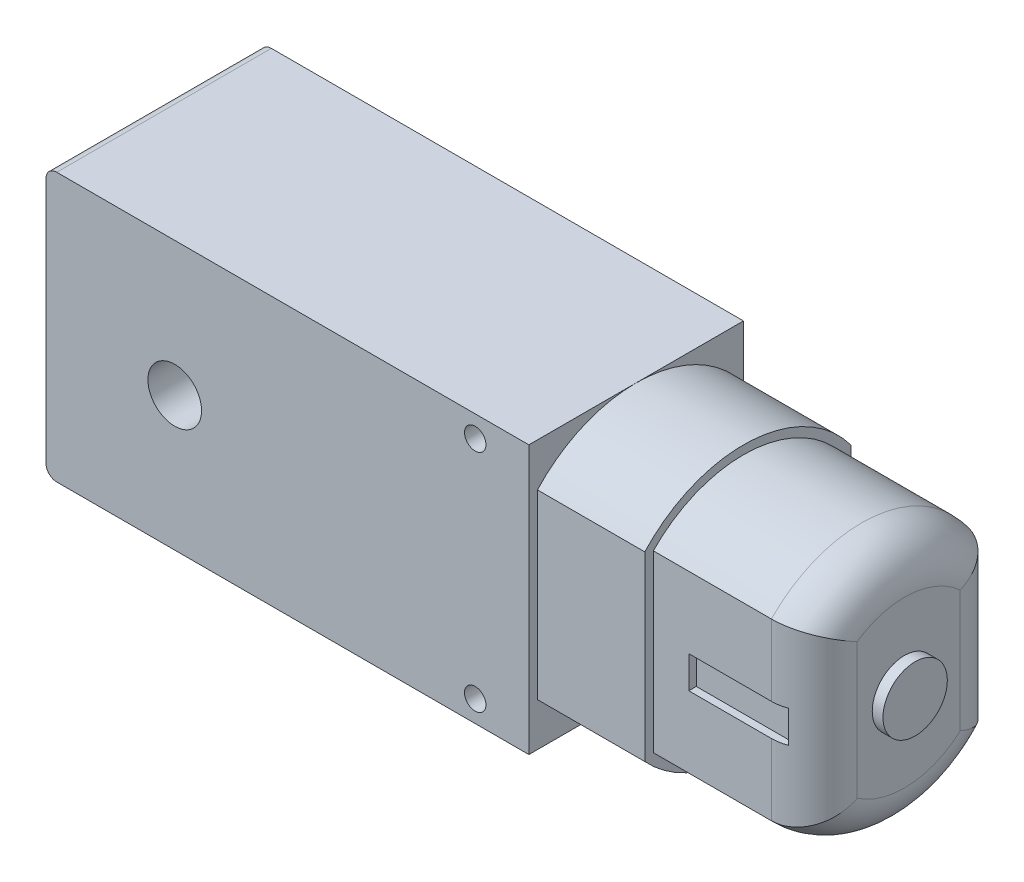
SolidWorks part; units mm, degrees
ref_plane "Front Plane" through (0, 0, 0) normal (0, 0, 1) x (1, 0, 0)
ref_plane "Top Plane" through (0, 0, 0) normal (0, 1, 0) x (1, 0, 0)
ref_plane "Right Plane" through (0, 0, 0) normal (1, 0, 0) x (0, 0, -1)
sketch "Sketch1" plane through (0, 0, 0) normal (0, 0, 1) x (1, 0, 0)
  line L1 (35, -12.5) -> (-35, -12.5)
  line L2 (35, -12.5) -> (35, 12.5)
  line L3 (35, 12.5) -> (-35, 12.5)
  line L4 (-35, -12.5) -> (-35, 12.5)
  line L5 (35, -12.5) -> (-35, 12.5) construction
  line L6 (35, 12.5) -> (-35, -12.5) construction
  point P0 (0, 0)
  dimension "D1" = 70
  dimension "D2" = 25
extrude "Boss-Extrude1" add sketch "Sketch1" along normal mid plane 20
sketch "Sketch2" plane through (35, 0, 0) normal (1, 0, 0) x (0, 0, -1)
  line L1 (-10, -7.5) -> (-10, -12.5)
  line L2 (10, 7.5) -> (10, 12.5)
  line L5 (10, -12.5) -> (10, 12.5)
  line L6 (10, 12.5) -> (-10, 12.5)
  line L7 (-10, 12.5) -> (-10, -12.5)
  line L8 (-10, -12.5) -> (10, -12.5)
  line L9 (10, -12.5) -> (10, -7.5)
  line L10 (10, 12.5) -> (-10, 12.5)
  line L11 (-10, 12.5) -> (-10, 7.5)
  line L12 (-10, -12.5) -> (10, -12.5)
  arc A0 (-10, -7.5) -> (10, -7.5) centre (0, 0) ccw
  arc A1 (10, 7.5) -> (-10, 7.5) centre (0, 0) ccw
  line M6 (10, -12.5) -> (10, 12.5)
  line M7 (10, 12.5) -> (-10, 12.5)
  line M8 (-10, 12.5) -> (-10, -12.5)
  line M9 (-10, -12.5) -> (10, -12.5)
  dimension "D1" = 0
extrude "Cut-Extrude2" cut sketch "Sketch2" against normal blind 25 contours A1 L10 M8 | A1 M6 M7 | A0 L12 M6 | A0 M8 M9 region at (35, -11.0705, 7.611) region at (35, 11.0705, 7.611) region at (35, -11.0705, -7.611) region at (35, 11.0705, -7.611)
sketch "Sketch4" plane through (35, 0, 0) normal (1, 0, 0) x (0, 0, -1)
  line L0 (-9.2, 8.4623) -> (-9.2, -8.4623)
  line L1 (-10, -7.5) -> (-10, 7.5) construction
  line L2 (-9.2, 8.4623) -> (-11.6207, 8.4623)
  line L3 (-11.6207, 8.4623) -> (-11.6207, -8.4623)
  line L4 (-11.6207, -8.4623) -> (-9.2, -8.4623)
  arc A0 (10, 7.5) -> (-10, 7.5) centre (0, 0) ccw construction
  arc A1 (-10, -7.5) -> (10, -7.5) centre (0, 0) ccw construction
  dimension "D1" = 0.8
extrude "Cut-Extrude3" cut sketch "Sketch4" against normal blind 25
sketch "Sketch5" plane through (35, 0, 0) normal (1, 0, 0) x (0, 0, -1)
  line L2 (-8.4, 8.1443) -> (-8.4, -8.1443)
  line L3 (9.2, -7.2284) -> (9.2, 7.2284)
  line L4 (-9.2, 8.4623) -> (-9.2, -8.4623)
  line L5 (10, -7.5) -> (10, 7.5)
  line L6 (-9.2, 8.4623) -> (-9.2, -8.4623)
  line L7 (10, -7.5) -> (10, 7.5)
  arc A2 (9.2, 7.2284) -> (-8.4, 8.1443) centre (0, 0) ccw
  arc A3 (-8.4, -8.1443) -> (9.2, -7.2284) centre (0, 0) ccw
  arc A4 (10, 7.5) -> (-9.2, 8.4623) centre (0, 0) ccw
  arc A5 (-9.2, -8.4623) -> (10, -7.5) centre (0, 0) ccw
  arc A6 (10, 7.5) -> (-9.2, 8.4623) centre (0, 0) ccw
  arc A7 (-9.2, -8.4623) -> (10, -7.5) centre (0, 0) ccw
  dimension "D1" = 0
  dimension "D2" = 0.8
extrude "Cut-Extrude4" cut sketch "Sketch5" against normal blind 15
fillet "Fillet1" radius 4 4 edges at (35, 0, -9.2) (35, -11.6842, -0.608) (35, 0, 8.4) (35, 11.6842, -0.608)
sketch "Sketch6" plane through (35, 0, 0) normal (1, 0, 0) x (0, 0, -1)
  circle A0 centre (0, 0) radius 3
  dimension "D1" = 6
extrude "Boss-Extrude2" add sketch "Sketch6" along normal blind 1
sketch "Sketch7" plane through (0, 0, -9.2) normal (0, 0, -1) x (-1, 0, 0)
  line L0 (-31, 7.2284) -> (-31, -7.2284) construction
  line L1 (-32.3651, -1.5) -> (-23.3004, -1.5)
  line L2 (-32.3651, -1.5) -> (-32.3651, 1.5)
  line L3 (-32.3651, 1.5) -> (-23.3004, 1.5)
  line L4 (-23.3004, -1.5) -> (-23.3004, 1.5)
  point P6 (-31, 0)
  point P7 (-23.3004, 0)
  dimension "D1" = 3
extrude "Cut-Extrude5" cut sketch "Sketch7" against normal blind 1.5
mirror "Mirror1" about plane through (0, 0, 0) normal (0, 0, 1) of "Cut-Extrude5"
fillet "Fillet2" radius 1 2 edges at (-35, 12.5, 0) (-35, -12.5, 0)
sketch "Sketch8" plane through (0, 0, 0) normal (0, 0, 1) x (1, 0, 0)
  line L0 (-35, 11.5) -> (-35, -11.5) construction
  line L1 (-35, -2.5) -> (-40, -2.5)
  line L2 (-35, -2.5) -> (-35, 2.5)
  line L3 (-35, 2.5) -> (-40, 2.5)
  line L4 (-40, -2.5) -> (-40, 2.5)
  circle A0 centre (-37.5, 0) radius 1.5
  point P6 (-40, 0)
  dimension "D3" = 3
  dimension "D1" = 5
  dimension "D2" = 5
extrude "Boss-Extrude3" add sketch "Sketch8" along normal mid plane 3.5
sketch "Sketch9" plane through (0, 0, 10) normal (0, 0, 1) x (1, 0, 0)
  line L0 (8.2693, 0) -> (-21.3687, 0) construction
  line L1 (-34, -12.5) -> (10, -12.5) construction
  line L2 (-35, 11.5) -> (-35, -11.5) construction
  circle A0 centre (5, -10.5) radius 1
  circle A1 centre (5, 10.5) radius 1
  dimension "D1" = 2
  dimension "D2" = 2
  dimension "D3" = 40
extrude "Cut-Extrude7" cut sketch "Sketch9" along normal through all and the other way through all
sketch "Sketch10" plane through (0, 0, -10) normal (0, 0, -1) x (-1, 0, 0)
  line L0 (35, 11.5) -> (35, -11.5) construction
  circle A0 centre (23, 0) radius 2.5
  dimension "D2" = 5
  dimension "D1" = 12
extrude "Cut-Extrude8" cut sketch "Sketch10" against normal through all
sketch "Sketch11" plane through (0, 0, 10) normal (0, 0, 1) x (1, 0, 0)
  line L0 (5, 10.5) -> (5, -10.5)
